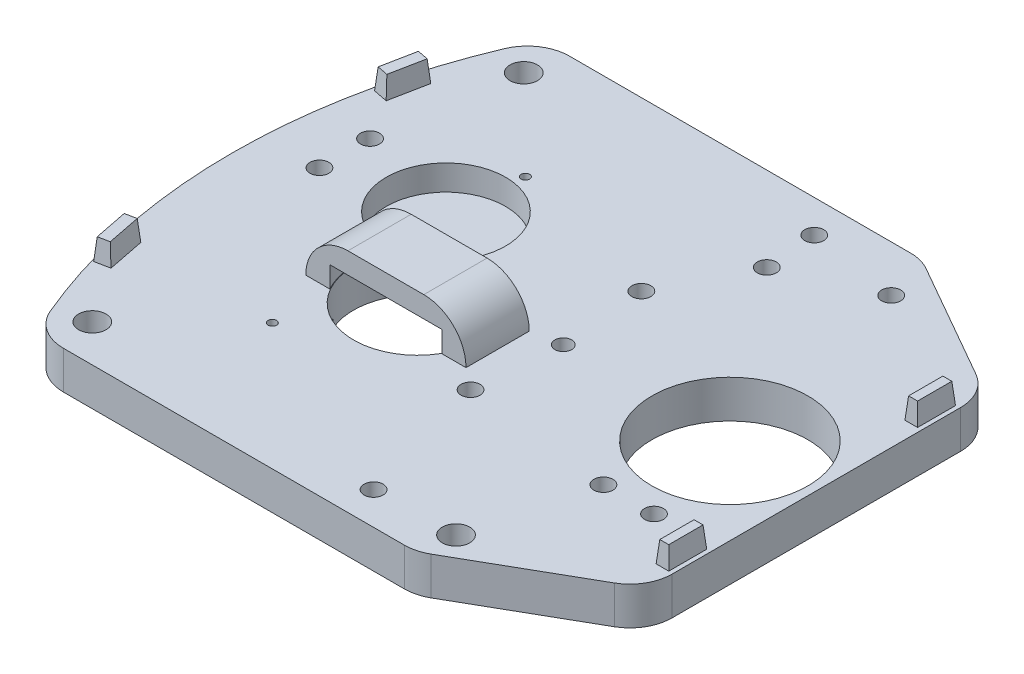
SolidWorks part; units mm, degrees
ref_plane "Front" through (0, 0, 0) normal (0, 0, 1) x (1, 0, 0)
ref_plane "Top" through (0, 0, 0) normal (0, 1, 0) x (1, 0, 0)
ref_plane "Right" through (0, 0, 0) normal (1, 0, 0) x (0, 0, -1)
sketch "Sketch1" plane through (0, 0, 0) normal (0, 1, 0) x (1, 0, 0)
  line L0 (125, 60) -> (3.8854, 60) construction
  line L1 (0, 0) -> (125, 0)
  line L2 (0, 0) -> (0, 120)
  line L3 (0, 120) -> (125, 120)
  line L4 (125, 0) -> (125, 120)
  line L5 (3.8854, 127.5) -> (3.8854, -7.5) construction
  arc A0 (3.8854, 127.5) -> (3.8854, -7.5) centre (125, 60) ccw
  dimension "D1" = 125
  dimension "D2" = 120
  dimension "D3" = 135
extrude "Top_Base" add sketch "Sketch1" along normal blind 9 contours L2 A0 | L1 L4 L3 L2 region at (62.5, 0, -60) region at (-5.4854, 0, -60)
sketch "Fingers_Position" plane through (0, 9, 0) normal (0, 1, 0) x (1, 0, 0)
  line L5 (67.75, 3.25) -> (12.75, 3.25) construction
  line L6 (67.75, 3.25) -> (67.75, 35.25) construction
  line L7 (67.75, 35.25) -> (12.75, 35.25) construction
  line L8 (12.75, 3.25) -> (12.75, 35.25) construction
  line L10 (67.75, 19.25) -> (26, 19.25) construction
  line L11 (77.75, 104.5) -> (77.75, 49.5) construction
  line L12 (35.75, 35.25) -> (35.75, 3.25) construction
  line L13 (40.75, 35.25) -> (40.75, 3.25) construction
  line L14 (125, 60) -> (-13.6542, 60) construction
  line L15 (35.75, 84.75) -> (35.75, 116.75) construction
  line L16 (26, 19.25) -> (26, 30) construction
  line L18 (77.75, 49.5) -> (109.75, 49.5) construction
  line L19 (109.75, 49.5) -> (109.75, 104.5) construction
  line L20 (109.75, 104.5) -> (77.75, 104.5) construction
  line L21 (92.5, 69) -> (92.5, 31) construction
  line L22 (92.5, 31) -> (116.5, 31) construction
  line L23 (116.5, 31) -> (116.5, 69) construction
  line L24 (116.5, 69) -> (92.5, 69) construction
  line L25 (93.75, 104.5) -> (93.75, 60) construction
  line L26 (104.5, 31) -> (104.5, 60) construction
  line L27 (26, 100.75) -> (26, 90) construction
  line L28 (40.75, 84.75) -> (40.75, 116.75) construction
  line L29 (67.75, 100.75) -> (26, 100.75) construction
  line L30 (12.75, 116.75) -> (12.75, 84.75) construction
  line L31 (67.75, 84.75) -> (12.75, 84.75) construction
  line L32 (67.75, 116.75) -> (67.75, 84.75) construction
  line L33 (67.75, 116.75) -> (12.75, 116.75) construction
  line L34 (26, 72.5) -> (26, 47.5) construction
  line L35 (92.5, 36) -> (98.5, 36) construction
  line L36 (98.5, 36) -> (98.5, 31) construction
  line L37 (116.5, 36) -> (110.5, 36) construction
  line L38 (110.5, 36) -> (110.5, 31) construction
  line L39 (93.75, 60) -> (104.5, 60) construction
  line L40 (77.75, 77.5) -> (109.75, 77.5) construction
  line L41 (125, 0) -> (125, 120) construction
  circle A1 centre (26, 30) radius 16.25 construction
  circle A3 centre (26, 30) radius 17.5 construction
  circle A5 centre (26, 30) radius 15 construction
  circle A6 centre (104.5, 60) radius 9 construction
  circle A7 centre (104.5, 60) radius 17.75 construction
  circle A8 centre (26, 30) radius 1 construction
  circle A9 centre (39.1696, 51.25) radius 7.5 construction
  circle A10 centre (39.1696, 51.25) radius 8.75 construction
  circle A11 centre (39.1696, 51.25) radius 10 construction
  circle A12 centre (39.1696, 68.75) radius 10 construction
  circle A13 centre (39.1696, 68.75) radius 8.75 construction
  circle A14 centre (39.1696, 68.75) radius 7.5 construction
  circle A15 centre (26, 90) radius 1 construction
  circle A16 centre (26, 90) radius 15 construction
  circle A17 centre (26, 90) radius 17.5 construction
  circle A18 centre (26, 90) radius 16.25 construction
  circle A19 centre (98.5, 36) radius 2.25 construction
  circle A20 centre (110.5, 36) radius 2.25 construction
  arc A21 (0, 120) -> (0, 0) centre (125, 60) ccw construction
  dimension "D3" = 32.5
  dimension "D4" = 35
  dimension "D6" = 30
  dimension "D10" = 18
  dimension "D11" = 35.5
  dimension "D19" = 2
  dimension "D20" = 20
  dimension "D21" = 17.5
  dimension "D22" = 15
  dimension "D29" = 4.5
  dimension "D5" = 32
  dimension "D7" = 55
  dimension "D8" = 24
  dimension "D9" = 38
  dimension "D14" = 10
  dimension "D2" = 27
  dimension "D15" = 55
  dimension "D16" = 32
  dimension "D17" = 41.75
  dimension "D18" = 10.75
  dimension "D23" = 25
  dimension "D13" = 29
  dimension "D25" = 6
  dimension "D26" = 6
  dimension "D27" = 5
  dimension "D28" = 5
  dimension "D12" = 44.5
  dimension "D30" = 10.75
  dimension "D31" = 27
  dimension "D24" = 8.5
  dimension "D32" = 32
sketch "Intermediate_Gear_Position" plane through (0, 9, 0) normal (0, 1, 0) x (1, 0, 0)
  line L0 (-5.25, 73.4139) -> (23.75, 73.4139) construction
  line L1 (35.75, 84.75) -> (35.75, 116.75) construction
  line L2 (32.75, 85.4139) -> (32.75, 61.4139) construction
  line L3 (-0.25, 79.4139) -> (-0.25, 85.4139) construction
  line L4 (32.75, 85.4139) -> (-5.25, 85.4139) construction
  line L6 (-5.25, 85.4139) -> (-5.25, 61.4139) construction
  line L7 (32.75, 61.4139) -> (-5.25, 61.4139) construction
  line L21 (-0.25, 67.4139) -> (-0.25, 61.4139) construction
  circle A0 centre (39.1696, 51.25) radius 14 construction
  circle A4 centre (39.1696, 51.25) radius 15 construction
  circle A6 centre (23.75, 73.4139) radius 14 construction
  circle A8 centre (39.1696, 51.25) radius 13 construction
  circle A10 centre (-0.25, 67.4139) radius 2.25 construction
  circle A11 centre (23.75, 73.4139) radius 13 construction
  circle A12 centre (-0.25, 79.4139) radius 2.25 construction
  circle A13 centre (23.75, 73.4139) radius 12 construction
  dimension "D2" = 30
  dimension "D6" = 28
  dimension "D4" = 26
  dimension "D18" = 4.5
  dimension "D22" = 4.5
  dimension "D3" = 28
  dimension "D10" = 26
  dimension "D11" = 24
  dimension "D8" = 38
  dimension "D5" = 6
  dimension "D7" = 24
  dimension "D16" = 5
  dimension "D19" = 6
  dimension "D21" = 5
  dimension "D9" = 29
  dimension "D12" = 3
sketch "Sketch5" plane through (0, 9, 0) normal (0, 1, 0) x (1, 0, 0)
  circle A1 centre (23.75, 73.4139) radius 14.15
  dimension "D1" = 28.3
extrude "Drive_Gear_Hole" cut sketch "Sketch5" against normal blind 6
sketch "Sketch8" plane through (0, 9, 0) normal (0, 1, 0) x (1, 0, 0)
  circle A1 centre (104.5, 60) radius 18.5
  dimension "D2" = 37
sketch "Sketch28" plane through (0, 9, 0) normal (0, 1, 0) x (1, 0, 0)
  circle A0 centre (39.1696, 51.25) radius 15.15
  dimension "D1" = 30.3
extrude "Two_Stage_Gear_Hole" cut sketch "Sketch28" against normal through all
extrude "XL320_Finger_Knuckle_Mount" cut sketch "Sketch8" against normal through all
sketch "XL320_Mount_Holes" plane through (0, 9, 0) normal (0, 1, 0) x (1, 0, 0)
  line L0 (116.5, 36) -> (110.5, 36) construction
  circle A13 centre (110.5, 36) radius 2.25
  circle A15 centre (98.5, 36) radius 2.25
  circle A16 centre (-0.25, 79.4139) radius 2.25
  circle A17 centre (-0.25, 67.4139) radius 2.25
  dimension "D5" = 4.5
sketch "AX12_Mount_Holes" plane through (0, 9, 0) normal (0, 1, 0) x (1, 0, 0)
  line L0 (67.75, 116.75) -> (72.25, 116.75) construction
  line L1 (67.75, 116.75) -> (12.75, 116.75) construction
  line L2 (72.25, 116.75) -> (72.25, 112.25) construction
  line L3 (67.75, 84.75) -> (67.75, 80.25) construction
  line L4 (67.75, 80.25) -> (63.25, 80.25) construction
  line L5 (93.75, 104.5) -> (93.75, 109) construction
  line L7 (109.75, 104.5) -> (77.75, 104.5) construction
  line L8 (77.75, 104.5) -> (73.25, 104.5) construction
  line L9 (73.25, 104.5) -> (73.25, 100) construction
  line L10 (67.75, 35.25) -> (67.75, 39.75) construction
  line L11 (67.75, 39.75) -> (63.25, 39.75) construction
  line L12 (67.75, 3.25) -> (72.25, 3.25) construction
  line L13 (67.75, 3.25) -> (12.75, 3.25) construction
  line L14 (72.25, 3.25) -> (72.25, 7.75) construction
  circle A4 centre (72.25, 112.25) radius 2.25
  circle A5 centre (63.25, 80.25) radius 2.25
  circle A6 centre (73.25, 100) radius 2.25
  circle A7 centre (93.75, 109) radius 2.25
  circle A8 centre (63.25, 39.75) radius 2.25
  circle A9 centre (72.25, 7.75) radius 2.25
  dimension "D2" = 4.5
  dimension "D1" = 4.5
sketch "Sketch26" plane through (0, 9, 0) normal (0, -1, 0) x (1, 0, 0)
  line L0 (26, -12.5) -> (26, -30) construction
  line L2 (-13.6542, -60) -> (125, -60) construction
  circle A0 centre (26, -30) radius 17.5 construction
  circle A1 centre (26, -30) radius 1
  circle A2 centre (26, -90) radius 1
  dimension "D2" = 2
extrude "String_Holes" cut sketch "Sketch26" along normal through all
extrude "XL320_Mount_Holes_(M4)" cut sketch "XL320_Mount_Holes" against normal through all
extrude "AX12_Mount_Holes_(M4)" cut sketch "AX12_Mount_Holes" against normal through all
sketch "Sketch27" plane through (0, 0, 0) normal (0, -1, 0) x (1, 0, 0)
  line L0 (110.5, -31.9585) -> (107, -33.9793)
  line L2 (107, -33.9793) -> (107, -38.0207)
  line L3 (107, -38.0207) -> (110.5, -40.0415)
  line L5 (110.5, -40.0415) -> (114, -38.0207)
  line L6 (114, -38.0207) -> (114, -33.9793)
  line L8 (114, -33.9793) -> (110.5, -31.9585)
  line L13 (110.5, -31.9585) -> (110.5, -40.0415) construction
  line L14 (107, -33.9793) -> (114, -38.0207) construction
  line L16 (114, -33.9793) -> (107, -38.0207) construction
  line L17 (98.5, -31.9585) -> (95, -33.9793)
  line L18 (95, -33.9793) -> (102, -38.0207) construction
  line L19 (95, -33.9793) -> (95, -38.0207)
  line L20 (102, -33.9793) -> (95, -38.0207) construction
  line L21 (98.5, -31.9585) -> (98.5, -40.0415) construction
  line L22 (102, -38.0207) -> (102, -33.9793)
  line L23 (95, -38.0207) -> (98.5, -40.0415)
  line L24 (98.5, -40.0415) -> (102, -38.0207)
  line L25 (102, -33.9793) -> (98.5, -31.9585)
  line L26 (3.25, -65.3931) -> (-0.25, -63.3724)
  line L27 (3.25, -69.4346) -> (3.25, -65.3931)
  line L28 (-3.75, -65.3931) -> (-3.75, -69.4346)
  line L29 (-0.25, -63.3724) -> (-0.25, -71.4553) construction
  line L30 (-3.75, -65.3931) -> (3.25, -69.4346) construction
  line L31 (-0.25, -63.3724) -> (-3.75, -65.3931)
  line L32 (-0.25, -71.4553) -> (3.25, -69.4346)
  line L33 (-3.75, -69.4346) -> (-0.25, -71.4553)
  line L34 (3.25, -65.3931) -> (-3.75, -69.4346) construction
  line L35 (-3.75, -77.3931) -> (3.25, -81.4346) construction
  line L36 (-3.75, -77.3931) -> (-3.75, -81.4346)
  line L37 (-0.25, -83.4553) -> (3.25, -81.4346)
  line L38 (-0.25, -75.3724) -> (-3.75, -77.3931)
  line L39 (3.25, -81.4346) -> (3.25, -77.3931)
  line L40 (-0.25, -75.3724) -> (-0.25, -83.4553) construction
  line L41 (3.25, -77.3931) -> (-0.25, -75.3724)
  line L42 (3.25, -77.3931) -> (-3.75, -81.4346) construction
  line L43 (-3.75, -81.4346) -> (-0.25, -83.4553)
  circle A4 centre (110.5, -36) radius 3.5 construction
  circle A5 centre (98.5, -36) radius 3.5 construction
  circle A6 centre (98.5, -36) radius 2.25 construction
  circle A7 centre (-0.25, -67.4139) radius 3.5 construction
  circle A8 centre (-0.25, -67.4139) radius 2.25 construction
  circle A9 centre (-0.25, -79.4139) radius 3.5 construction
  circle A21 centre (-0.25, -79.4139) radius 2.25 construction
  dimension "D1" = 7
  dimension "D3" = 7
  dimension "D5" = 7
  dimension "D7" = 7
  dimension "D2" = 60
  dimension "D4" = 60
  dimension "D6" = 60
  dimension "D8" = 60
extrude "Nuts_(M4)" cut sketch "Sketch27" against normal blind 5
sketch "Sketch34" plane through (0, 0, 0) normal (0, -1, 0) x (1, 0, 0)
  circle A0 centre (26, -30) radius 15
  circle A1 centre (26, -90) radius 15
  circle A2 centre (26, -90) radius 11.75 construction
  dimension "D1" = 30
  dimension "D2" = 23.5
extrude "Holes_For_M4_In_Finger_Gear" cut sketch "Sketch34" against normal blind 2
sketch "Sketch31" plane through (0, 9, 0) normal (0, 1, 0) x (1, 0, 0)
  line L1 (58.1696, 43.75) -> (20.1696, 43.75)
  line L2 (58.1696, 43.75) -> (58.1696, 58.75)
  line L3 (58.1696, 58.75) -> (20.1696, 58.75)
  line L4 (20.1696, 43.75) -> (20.1696, 58.75)
  line L5 (58.1696, 43.75) -> (20.1696, 58.75) construction
  line L6 (58.1696, 58.75) -> (20.1696, 43.75) construction
  point P0 (39.1696, 51.25)
  dimension "D1" = 38
  dimension "D2" = 15
extrude "Boss-Extrude1" add sketch "Sketch31" along normal blind 10
sketch "Sketch32" plane through (0, 9, 0) normal (0, -1, 0) x (1, 0, 0)
  circle A0 centre (39.1696, -51.25) radius 15.25
  dimension "D1" = 30.5
extrude "Cut-Extrude5" cut sketch "Sketch32" against normal blind 5
sketch "Sketch33" plane through (0, 14, 0) normal (0, -1, 0) x (1, 0, 0)
  circle A0 centre (39.1696, -51.25) radius 1
  dimension "D1" = 2
extrude "Cut-Extrude6" cut sketch "Sketch33" against normal blind 2.5
fillet "Fillet2" radius 10 2 edges at (58.1696, 19, -51.25) (20.1696, 19, -51.25)
sketch "Sketch36" plane through (0, 9, 0) normal (0, 1, 0) x (1, 0, 0)
  line L0 (90, 120) -> (125, 100)
  line L1 (0, 120) -> (125, 120) construction
  line L2 (125, 0) -> (125, 120) construction
  line L3 (125, 100) -> (125, 120)
  line L4 (125, 120) -> (90, 120)
  line L5 (-13.6542, 60) -> (125, 60) construction
  line L6 (125, 0) -> (90, 0)
  line L7 (125, 20) -> (125, 0)
  line L8 (90, 0) -> (125, 20)
  dimension "D1" = 35
  dimension "D4" = 20
extrude "Cut-Extrude8" cut sketch "Sketch36" against normal through all
fillet "Fillet4" radius 10 6 edges at (0, 4.5, 0) (90, 4.5, 0) (125, 4.5, -20) (125, 4.5, -100) (90, 4.5, -120) (0, 4.5, -120)
sketch "Sketch37" plane through (0, 9, 0) normal (0, 1, 0) x (1, 0, 0)
  line L0 (6.4592, 120) -> (6.4592, 0) construction
  line L1 (87.3444, 120) -> (87.3444, 0) construction
  line L2 (6.4592, 111.1529) -> (4.4592, 111.1529) construction
  line L3 (4.4592, 111.1529) -> (0.9304, 118.3326) construction
  line L4 (-13.6542, 60) -> (125, 60) construction
  line L5 (4.4592, 8.8471) -> (0.9304, 1.6674) construction
  line L6 (6.4592, 8.8471) -> (4.4592, 8.8471) construction
  line L7 (91.3444, 8.2056) -> (87.3444, 8.2056) construction
  line L10 (91.3444, 8.2056) -> (89.911, 0.335) construction
  arc A0 (87.3444, 0) -> (92.3057, 1.3176) centre (87.3444, 10) ccw construction
  circle A1 centre (4.4592, 111.1529) radius 3.25
  arc A2 (6.4592, 120) -> (-2.7547, 113.8864) centre (6.4592, 110) ccw construction
  circle A3 centre (4.4592, 8.8471) radius 3.25
  circle A4 centre (91.3444, 8.2056) radius 3.25
  dimension "D1" = 6.5
  dimension "D4" = 6.5
  dimension "D2" = 8
  dimension "D3" = 2
  dimension "D5" = 4
  dimension "D6" = 8
extrude "Connect_Holes_(M6)" cut sketch "Sketch37" against normal blind 10
sketch "Sketch41" plane through (0, 9, 0) normal (0, 1, 0) x (1, 0, 0)
  line L0 (125, 60) -> (-13.6542, 60) construction
  line L1 (125, 60) -> (65, 60) construction
  line L2 (125, 25.8032) -> (125, 94.1968) construction
  circle A0 centre (65, 60) radius 2
  dimension "D2" = 4
  dimension "D1" = 60
extrude "Connect_To_House_(M4)" cut sketch "Sketch41" against normal through all
sketch "Sketch42" plane through (0, 9, 0) normal (0, 1, 0) x (1, 0, 0)
  line L5 (-13.6542, 60) -> (125, 60) construction
  line L6 (124, 26) -> (121, 26)
  line L7 (124, 26) -> (124, 35)
  line L8 (124, 35) -> (121, 35)
  line L9 (121, 26) -> (121, 35)
  line L10 (-13.6542, 60) -> (-3.3496, 8.0542) construction
  line L11 (-9.5334, 30.2329) -> (-6.1003, 30.9139)
  line L12 (-6.1003, 30.9139) -> (-4.349, 22.0859)
  line L13 (-4.349, 22.0859) -> (-7.7822, 21.4049)
  line L14 (-7.7822, 21.4049) -> (-9.5334, 30.2329)
  line L15 (125, 25.8032) -> (125, 94.1968) construction
  line L16 (-4.349, 97.9141) -> (-7.7822, 98.5951)
  line L17 (-6.1003, 89.0861) -> (-4.349, 97.9141)
  line L18 (-7.7822, 98.5951) -> (-9.5334, 89.7671)
  line L19 (-9.5334, 89.7671) -> (-6.1003, 89.0861)
  line L20 (124, 94) -> (121, 94)
  line L21 (121, 94) -> (121, 85)
  line L22 (124, 85) -> (121, 85)
  line L23 (124, 94) -> (124, 85)
  arc A1 (-2.7547, 6.1136) -> (6.4592, 0) centre (6.4592, 10) ccw construction
  point P16 (-7.8168, 30.5734)
  dimension "D1" = 3
  dimension "D2" = 9
  dimension "D3" = 25
  dimension "D4" = 9
  dimension "D5" = 3.5
  dimension "D6" = 30
  dimension "D7" = 1
extrude "Housing_Fits" add sketch "Sketch42" along normal blind 5 draft 5
sketch "Sketch43" plane through (0, 0, 0) normal (0, -1, 0) x (1, 0, 0)
  circle A0 centre (39.1696, -68.75) radius 1
  dimension "D1" = 2
extrude "M2_Shaft_Hole" cut sketch "Sketch43" against normal blind 2
equation "\"od1\"= 35'outside diameter finger"
equation "\"n1\"= 26'number of teeth finger"
equation "\"m1\"= \"od1\" / ( \"n1\" + 2 )'module finger"
equation "\"p1\"= \"m1\" * pi'pitch finger"
equation "\"d1\"= \"m1\" * \"n1\"'primitive diameter finger"
equation "\"da1\"= \"d1\" + 2 * \"m1\"'head diamater finger"
equation "\"df1\"= \"d1\" - 2 * \"m1\"'foot diameter finger"
equation "\"od2\"= 20'outside diameter intermediate"
equation "\"n2\"= 14'number of teeth intermediate"
equation "\"m2\"= \"od2\" / ( \"n2\" + 2 )'module intermediate"
equation "\"p2\"= \"m2\" * pi'pitch intermediate"
equation "\"d2\"= \"m2\" * \"n2\"'primitive diameter intermediate"
equation "\"da2\"= \"d2\" + 2 * \"m2\"'head diamater intermediate"
equation "\"df2\"= \"d2\" - 2 * \"m2\"'foot diameter intermediate"
equation "\"od3\"= 30'outside diameter top"
equation "\"n3\"= 28'number of teeth top"
equation "\"m3\"= \"od3\" / ( \"n3\" + 2 )'module top"
equation "\"p3\"= \"m3\" * pi'pitch top"
equation "\"d3\"= \"m3\" * \"n3\"'primitive diameter top"
equation "\"da3\"= \"d3\" + 2 * \"m3\"'head diamater top"
equation "\"df3\"= \"d3\" - 2 * \"m3\"'foot diameter top"
equation "\"od4\"= 28'outside diameter drive"
equation "\"n4\"= 26'number of teeth drive"
equation "\"m4\"= \"od4\" / ( \"n4\" + 2 )'module drive"
equation "\"p4\"= \"m4\" * pi'pitch drive"
equation "\"d4\"= \"m4\" * \"n4\"'primitive diameter drive"
equation "\"da4\"= \"d4\" + 2 * \"m4\"'head diamater drive"
equation "\"df4\"= \"d4\" - 2 * \"m4\"'foot diameter drive"
equation "\"D4@Fingers_Position\"=\"da1\""
equation "\"D3@Fingers_Position\"=\"d1\""
equation "\"D6@Fingers_Position\"=\"df1\""
equation "\"D20@Fingers_Position\"=\"da2\""
equation "\"D21@Fingers_Position\"=\"d2\""
equation "\"D22@Fingers_Position\"=\"df2\""
equation "\"D3@Intermediate_Gear_Position\"=\"d3\""
equation "\"D2@Intermediate_Gear_Position\"=\"da3\""
equation "\"D4@Intermediate_Gear_Position\"=\"df3\""
equation "\"D6@Intermediate_Gear_Position\"=\"da4\""
equation "\"D10@Intermediate_Gear_Position\"=\"d4\""
equation "\"D11@Intermediate_Gear_Position\"=\"df4\""
equation "\"D1@Sketch34\"=\"df1\""
